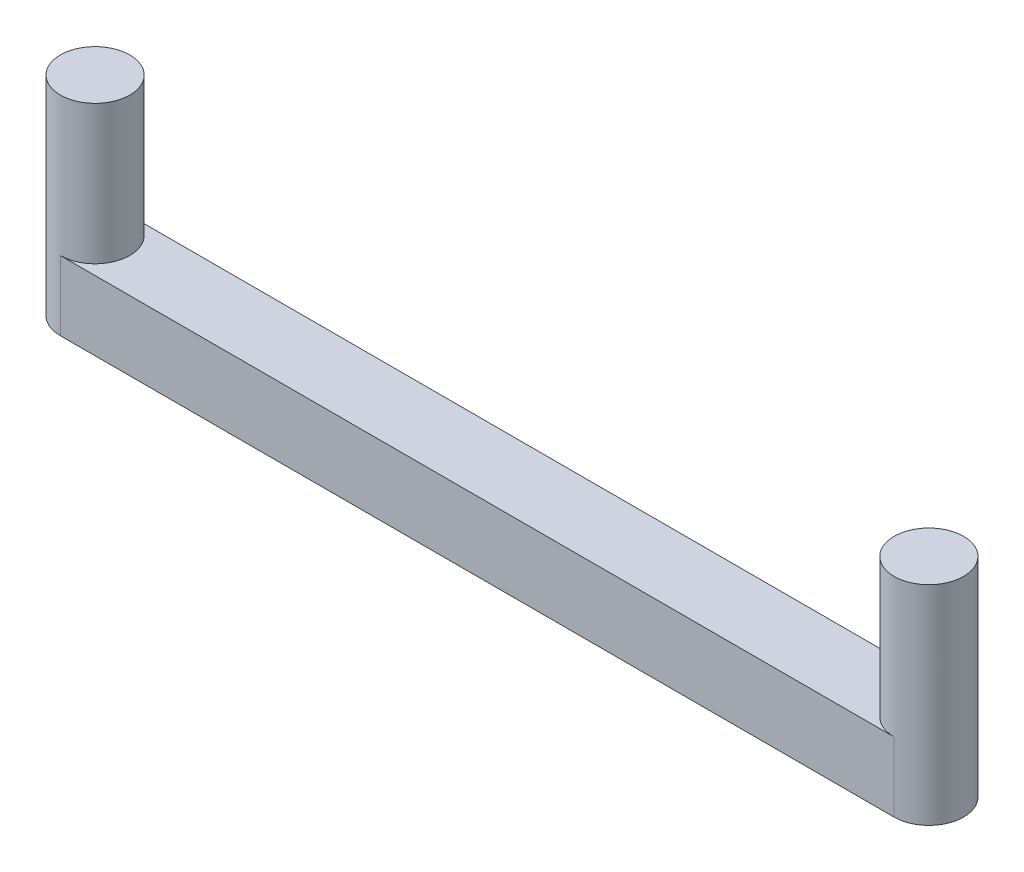
SolidWorks part; units mm, degrees
ref_plane "Alzado" through (0, 0, 0) normal (0, 0, 1) x (1, 0, 0)
ref_plane "Planta" through (0, 0, 0) normal (0, 1, 0) x (1, 0, 0)
ref_plane "Vista lateral" through (0, 0, 0) normal (1, 0, 0) x (0, 0, -1)
sketch "Croquis1" plane through (0, 0, 0) normal (0, 1, 0) x (1, 0, 0)
  line L1 (-60, -34.2075) -> (60, -34.2075)
  line L3 (-60, -44.2075) -> (60, -44.2075)
  arc A0 (60, -44.2075) -> (60, -34.2075) centre (60, -39.2075) ccw
  arc A1 (-60, -34.2075) -> (-60, -44.2075) centre (-60, -39.2075) ccw
  dimension "D1" = 5
  dimension "D2" = 5
  dimension "D3" = 120
extrude "Saliente-Extruir1" add sketch "Croquis1" along normal blind 10
sketch "Croquis2" plane through (0, 10, 0) normal (0, 1, 0) x (1, 0, 0)
  circle A0 centre (60, -39.2075) radius 5
  circle A1 centre (-60, -39.2075) radius 5
extrude "Saliente-Extruir2" add sketch "Croquis2" along normal blind 20
